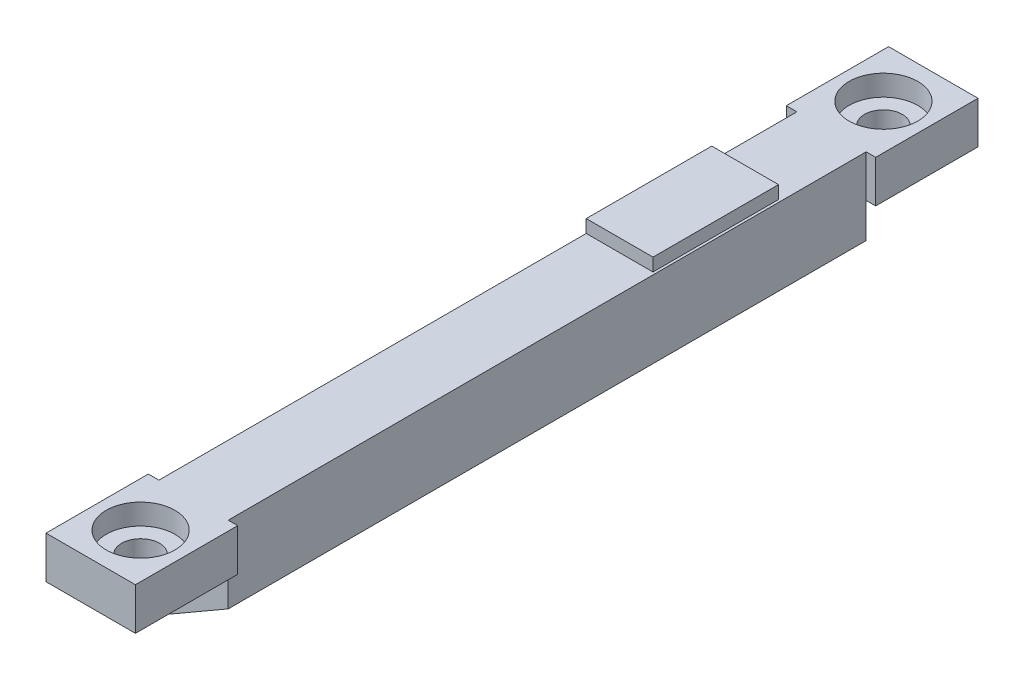
SolidWorks part; units mm, degrees
ref_plane "Front Plane" through (0, 0, 0) normal (0, 0, 1) x (1, 0, 0)
ref_plane "Top Plane" through (0, 0, 0) normal (0, 1, 0) x (1, 0, 0)
ref_plane "Right Plane" through (0, 0, 0) normal (1, 0, 0) x (0, 0, -1)
other "Configuration Table"
sketch "Sketch1" plane through (0, 0, 0) normal (0, 0, 1) x (1, 0, 0)
  line L0 (13.3671, -4) -> (17.3973, -4)
  line L1 (17.3973, -4) -> (17.3973, -8.4701)
  line L2 (17.3973, -8.4701) -> (13.3671, -10.7969)
  line L3 (13.3671, -10.7969) -> (13.3671, -4)
extrude "Clamp +X base" add sketch "Sketch1" along normal blind 37.1 from offset 20.15 offset against normal yes
sketch "Sketch2" plane through (0, 0, 0) normal (0, 0, 1) x (1, 0, 0)
  line L0 (12.75, -6.45) -> (17.95, -6.45)
  line L1 (17.95, -6.45) -> (17.95, -4)
  line L2 (17.95, -4) -> (12.75, -4)
  line L3 (12.75, -4) -> (12.75, -6.45)
extrude "Ear +X base -26" add sketch "Sketch2" along normal blind 5.95 from offset 26.1 offset against normal yes
sketch "Sketch3" plane through (0, 0, 0) normal (0, 0, 1) x (1, 0, 0)
  line L0 (12.75, -6.45) -> (17.95, -6.45)
  line L1 (17.95, -6.45) -> (17.95, -4)
  line L2 (17.95, -4) -> (12.75, -4)
  line L3 (12.75, -4) -> (12.75, -6.45)
extrude "Ear +X base 17" add sketch "Sketch3" along normal blind 5.95 from offset 16.95
sketch "Sketch4" plane through (0, 0, 0) normal (0, 1, 0) x (1, 0, 0)
  circle A0 centre (15.35, 23.2) radius 1.1
  circle A1 centre (15.35, -20) radius 1.1
extrude "Cut-Extrude1" cut sketch "Sketch4" along normal blind 2.65 from offset 6.55 offset against normal yes
sketch "Sketch5" plane through (0, 0, 0) normal (0, 1, 0) x (1, 0, 0)
  circle A0 centre (15.35, 23.2) radius 2
  circle A1 centre (15.35, -20) radius 2
extrude "Cut-Extrude2" cut sketch "Sketch5" along normal blind 1.22 from offset 5.21 offset against normal yes
sketch "Sketch6" plane through (0, 0, 0) normal (0, 1, 0) x (1, 0, 0)
  line L1 (13.3671, 15.2) -> (17.25, 15.2)
  line L2 (13.3671, 15.2) -> (13.3671, 7.9)
  line L3 (13.3671, 7.9) -> (17.25, 7.9)
  line L4 (17.25, 15.2) -> (17.25, 7.9)
extrude "Boss-Extrude4" add sketch "Sketch6" along normal blind 0.75 from offset 4 offset against normal yes
